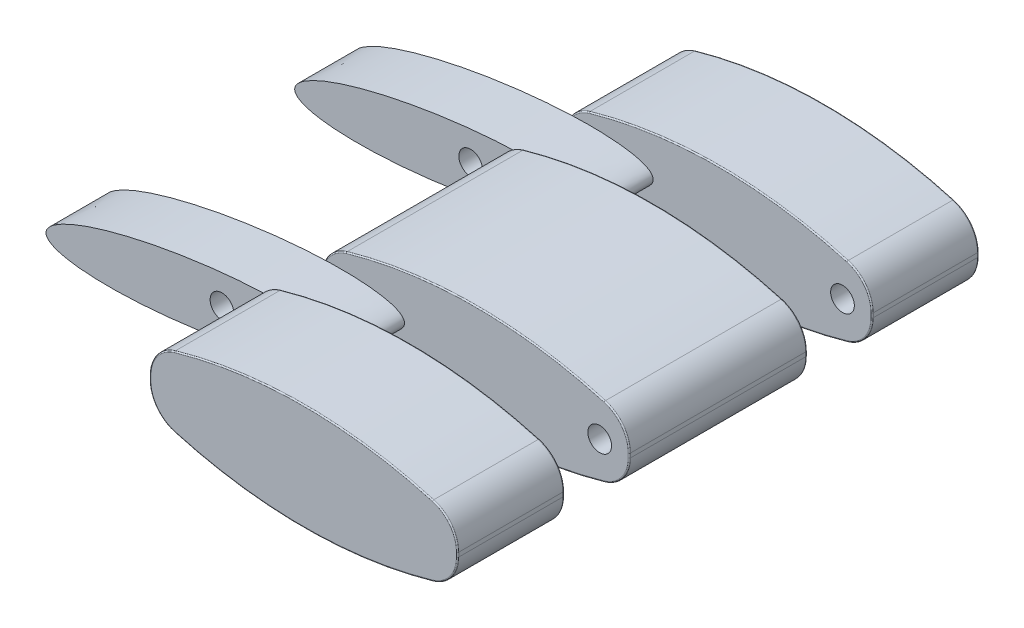
SolidWorks part; units mm, degrees
ref_plane "Front Plane" through (0, 0, 0) normal (0, 0, 1) x (1, 0, 0)
ref_plane "Top Plane" through (0, 0, 0) normal (0, 1, 0) x (1, 0, 0)
ref_plane "Right Plane" through (0, 0, 0) normal (1, 0, 0) x (0, 0, -1)
sketch "Sketch1" plane through (0, 0, 0) normal (0, 0, 1) x (1, 0, 0)
  line L0 (0, -55) -> (0, 55) construction
  line L2 (-6.5, 0.0896) -> (-6.5, -0.0896)
  line L4 (6.5, 0.0896) -> (6.5, -0.0896)
  arc A0 (-5.45, 1.4833) -> (5.45, 1.4833) centre (0, -17.5045) cw
  arc A1 (-5.45, -1.4833) -> (5.45, -1.4833) centre (0, 17.5045) ccw
  arc A2 (5.45, 1.4833) -> (6.5, 0.0896) centre (5.05, 0.0896) cw
  arc A3 (5.45, -1.4833) -> (6.5, -0.0896) centre (5.05, -0.0896) ccw
  arc A4 (-5.45, -1.4833) -> (-6.5, -0.0896) centre (-5.05, -0.0896) cw
  arc A5 (-5.45, 1.4833) -> (-6.5, 0.0896) centre (-5.05, 0.0896) ccw
  dimension "D1" = 1.45
  dimension "D2" = 6.5
extrude "Boss-Extrude1" add sketch "Sketch1" along normal blind 22
sketch "Sketch2" plane through (0, 0, 0) normal (0, 1, 0) x (1, 0, 0)
  line L0 (-2.475, 0) -> (2.475, 0) construction
  line L1 (-10.8182, -4.5) -> (10.0029, -4.5)
  line L2 (-10.8182, -4.5) -> (-10.8182, -7.25)
  line L3 (-10.8182, -7.25) -> (10.0029, -7.25)
  line L4 (10.0029, -4.5) -> (10.0029, -7.25)
  line L5 (-9.7834, -14.75) -> (12.5428, -14.75)
  line L6 (-9.7834, -14.75) -> (-9.7834, -17.5)
  line L7 (-9.7834, -17.5) -> (12.5428, -17.5)
  line L8 (12.5428, -14.75) -> (12.5428, -17.5)
  line L9 (-5.45, -22) -> (5.45, -22) construction
  dimension "D1" = 4.5
  dimension "D2" = 4.5
  dimension "D3" = 2.75
  dimension "D4" = 2.75
extrude "Cut-Extrude1" cut sketch "Sketch2" against normal mid plane 22
sketch "Sketch3" plane through (0, 0, 22) normal (0, 0, 1) x (1, 0, 0)
  line L0 (12.1, 0) -> (-12.1, 0) construction
  line L1 (0, -2.475) -> (0, 2.475) construction
  circle A0 centre (5.25, 0) radius 0.5
  circle A1 centre (-5.25, 0) radius 0.5
  dimension "D1" = 1
  dimension "D2" = 1
  dimension "D3" = 5.25
  dimension "D4" = 5.25
extrude "Cut-Extrude2" cut sketch "Sketch3" against normal blind 21 from offset 0.5 offset against normal yes
fillet "Fillet1" radius 0.05 16 edges at (6.2081, 0.9621, 17.5) (6.5, 0, 17.5) (6.2081, -0.9621, 17.5) (0, -2.25, 17.5) (-6.2081, -0.9621, 17.5) (-6.5, 0, 17.5) (-6.2081, 0.9621, 17.5) (6.5, 0, 22) (6.2081, -0.9621, 22) (0, -2.25, 22) (-6.2081, -0.9621, 22) (-6.5, 0, 22) (-6.2081, 0.9621, 22) (0, 2.25, 22) (6.2081, 0.9621, 22) (0, 2.25, 17.5)
fillet "Fillet2" radius 0.05 16 edges at (6.2081, 0.9621, 7.25) (6.5, 0, 7.25) (6.2081, -0.9621, 7.25) (0, -2.25, 7.25) (-6.2081, -0.9621, 7.25) (-6.5, 0, 7.25) (-6.2081, 0.9621, 7.25) (-6.2081, 0.9621, 14.75) (-6.5, 0, 14.75) (-6.2081, -0.9621, 14.75) (0, -2.25, 14.75) (6.2081, -0.9621, 14.75) (6.5, 0, 14.75) (6.2081, 0.9621, 14.75) (0, 2.25, 7.25) (0, 2.25, 14.75)
fillet "Fillet3" radius 0.05 16 edges at (6.2081, 0.9621, 0) (6.5, 0, 0) (6.2081, -0.9621, 0) (0, -2.25, 0) (-6.2081, -0.9621, 0) (-6.5, 0, 0) (-6.2081, 0.9621, 0) (-6.5, 0, 4.5) (-6.2081, -0.9621, 4.5) (0, -2.25, 4.5) (6.2081, -0.9621, 4.5) (6.5, 0, 4.5) (6.2081, 0.9621, 4.5) (0, 2.25, 4.5) (0, 2.25, 0) (-6.2081, 0.9621, 4.5)
sketch "Sketch4" plane through (0, 0, 4.5) normal (0, 0, 1) x (1, 0, 0)
  circle A0 centre (5.25, 0) radius 0.5
  dimension "D1" = 1
extrude "Cut-Extrude3" cut sketch "Sketch4" against normal mid plane 60
sketch "Sketch6" plane through (0, 0, 22) normal (0, 0, 1) x (1, 0, 0)
  ellipse E0 centre (-9.0588, -0.5158) end of major axis (-2.7434, 0.3987) minor radius 1.231
extrude "Boss-Extrude2" add sketch "Sketch6" against normal blind 2.5 from offset 4.5 offset against normal yes
extrude "Boss-Extrude3" add sketch "Sketch6<2>" along normal blind 2.5 from offset 17.5 offset against normal yes
sketch "Sketch6<2>" plane through (0, 0, 22) normal (0, 0, 1) x (1, 0, 0) same geometry as "Sketch6"
sketch "Sketch7" plane through (0, 0, 17.5) normal (0, 0, 1) x (1, 0, 0)
  circle A0 centre (-7.9476, -0.3774) radius 0.5
  dimension "D1" = 1
extrude "Cut-Extrude6" cut sketch "Sketch7" against normal blind 22.5
sketch "Sketch8" [suppressed] plane through (0, 0, 0) normal (0, 1, 0) x (1, 0, 0)
  line L0 (-0.2, -20.7889) -> (0.2, -20.7889)
  line L1 (-0.2, -20.7889) -> (-0.2, -19.2889)
  line L2 (0.2, -20.7889) -> (0.2, -19.2889)
  line L3 (-0.2, -19.2889) -> (-0.45, -19.2889)
  line L4 (-0.45, -19.2889) -> (0, -18.6389)
  line L5 (0, -18.6389) -> (0.45, -19.2889)
  line L6 (0.45, -19.2889) -> (0.2, -19.2889)
  line L7 (0.2, -19.2889) -> (0.2001, -19.2946)
  dimension "D1" = 0.4
  dimension "D2" = 1.5
  dimension "D3" = 0.25
  dimension "D4" = 0.25
sketch "Sketch9" plane through (0, 0, 22) normal (0, 0, 1) x (1, 0, 0)
  circle A0 centre (5.25, 0) radius 0.6427
extrude "Boss-Extrude4" add sketch "Sketch9" against normal blind 0.5
sketch "Sketch10" plane through (0, 0, 0) normal (0, 0, -1) x (-1, 0, 0)
  circle A0 centre (-5.25, 0) radius 0.7493
extrude "Boss-Extrude5" add sketch "Sketch10" against normal blind 0.5
